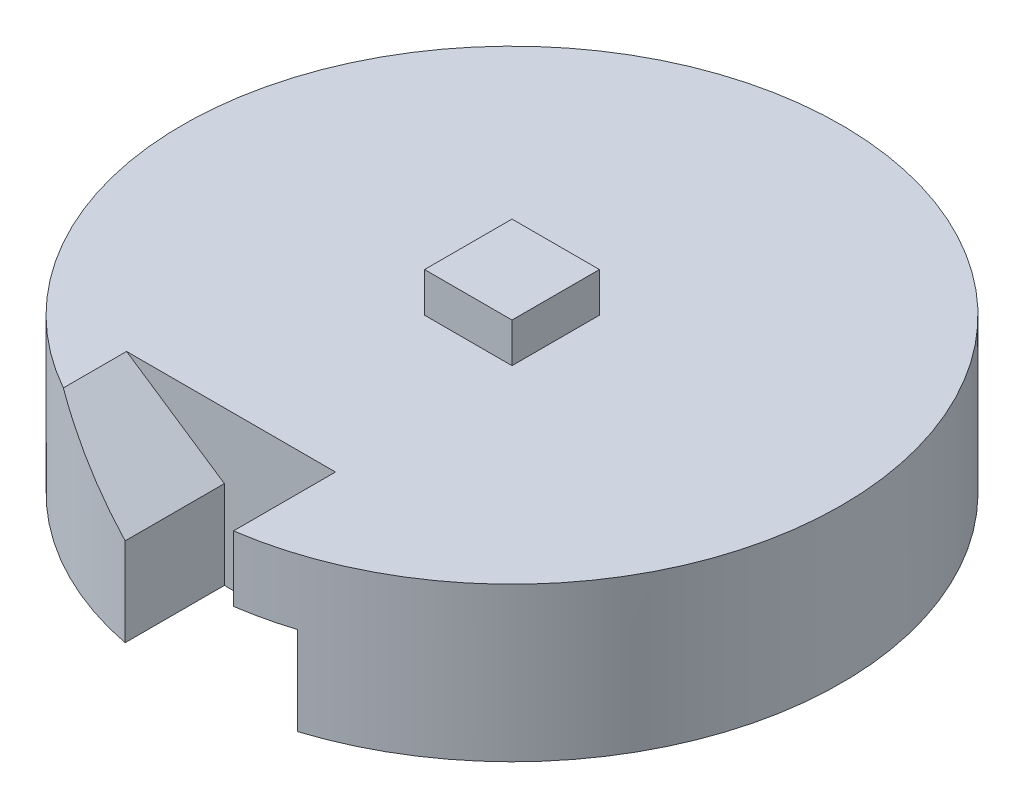
SolidWorks part; units mm, degrees
ref_plane "Front Plane" through (0, 0, 0) normal (0, 0, 1) x (1, 0, 0)
ref_plane "Top Plane" through (0, 0, 0) normal (0, 1, 0) x (1, 0, 0)
ref_plane "Right Plane" through (0, 0, 0) normal (1, 0, 0) x (0, 0, -1)
sketch "Sketch1" plane through (0, 0, 0) normal (0, 1, 0) x (1, 0, 0)
  circle A0 centre (0, 0) radius 37.5
extrude "Boss-Extrude1" add sketch "Sketch1" along normal blind 17.5 contours A0
sketch "Sketch2" plane through (0, 0, 0) normal (0, -1, 0) x (1, 0, 0)
  circle A0 centre (0, 0) radius 5
sketch "Sketch3" plane through (0, 17.5, 0) normal (0, 1, 0) x (1, 0, 0)
  line L0 (0, -75) -> (0, -65)
  line L1 (0, -65) -> (11.5, -65)
  line L2 (0, -65) -> (-11.5, -65)
  line L3 (-11.5, -65) -> (-11.5, -73.5674)
  line L4 (11.5, -65) -> (11.5, -73.5674)
  arc A0 (-37.5, 0) -> (37.5, 0) centre (0, -28.125) ccw
  circle A1 centre (0, 0) radius 37.5 construction
ref_plane "Plane1" through (0, 0, 37.5) normal (0, 0, 1) x (1, 0, 0)
sketch "Sketch7" plane through (0, 0, 37.5) normal (0, 0, 1) x (1, 0, 0)
  line L8 (5.4092, 17.6699) -> (-18.6153, 17.6699)
  line L18 (-18.6153, 17.6699) -> (-7.232, 10.0401)
  line L19 (5.4092, 17.6699) -> (5.4092, 10.0587)
  line L20 (5.4092, 10.0587) -> (11.3378, 10.0587)
  line L21 (11.3378, 10.0587) -> (11.3378, -0.1861)
  line L22 (-7.232, 10.0401) -> (-7.232, -0.1861)
  line L23 (-7.232, -0.1861) -> (11.3378, -0.1861)
extrude "Cut-Extrude3" cut sketch "Sketch7" against normal blind 12
sketch "Sketch9" plane through (0, 0, 0) normal (0, 1, 0) x (1, 0, 0)
  line L1 (-4.975, 4.975) -> (4.975, 4.975)
  line L2 (-4.975, 4.975) -> (-4.975, -4.975)
  line L3 (-4.975, -4.975) -> (4.975, -4.975)
  line L4 (4.975, 4.975) -> (4.975, -4.975)
  line L5 (-4.975, 4.975) -> (4.975, -4.975) construction
  line L6 (-4.975, -4.975) -> (4.975, 4.975) construction
  point P0 (0, 0)
  dimension "D1" = 9.95
  dimension "D2" = 9.95
extrude "Boss-Extrude2" add sketch "Sketch9" along normal blind 22
extrude "Boss-Extrude3" add sketch "Sketch2" along normal blind 5 contours A0
sketch "Sketch11" plane through (0, -5, 0) normal (0, -1, 0) x (1, 0, 0)
  line L4 (0.0346, -0.0411) -> (0.0346, 1.4839)
  line L5 (0.0346, 1.4839) -> (-2.4654, 1.4839)
  line L6 (-2.4654, 1.4839) -> (-2.4654, -1.5161)
  line L7 (-2.4654, -1.5161) -> (2.5346, -1.5161)
  line L8 (2.5346, -1.5161) -> (2.5346, 1.4839)
  line L9 (2.5346, 1.4839) -> (0.0346, 1.4839)
  point P3 (0, 0)
  point P4 (0, 0)
extrude "Cut-Extrude7" cut sketch "Sketch11" against normal blind 10 contours L5 L6 L7 L8 L9
sketch "Sketch12" plane through (0, 0, 0) normal (0, -1, 0) x (-1, 0, 0)
  circle A3 centre (-30.018, -0.0068) radius 3.025
  circle A4 centre (29.982, -0.0068) radius 3.025
extrude "Cut-Extrude6" cut sketch "Sketch12" against normal blind 1.6 contours A3 | A4
